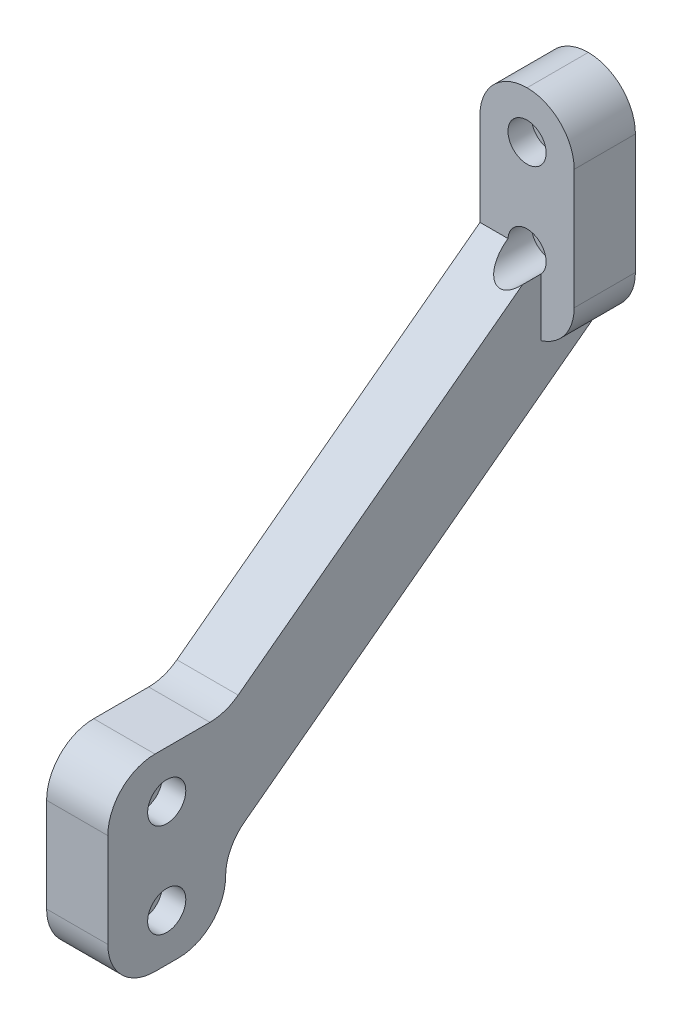
SolidWorks part; units mm, degrees
ref_plane "Alzado" through (0, 0, 0) normal (0, 0, 1) x (1, 0, 0)
ref_plane "Planta" through (0, 0, 0) normal (0, 1, 0) x (1, 0, 0)
ref_plane "Vista lateral" through (0, 0, 0) normal (1, 0, 0) x (0, 0, -1)
sketch "Croquis1" plane through (0, 0, 0) normal (1, 0, 0) x (0, 0, -1)
  line L0 (0, 0) -> (0, 40)
  line L1 (0, 40) -> (25, 40)
  line L2 (25, 40) -> (92, 90.25)
  line L3 (92, 90.25) -> (92, 120)
  line L4 (92, 120) -> (105, 120)
  line L5 (105, 120) -> (105, 75)
  line L7 (25, 0) -> (0, 0)
  line L8 (105, 75) -> (25, 15)
  line L9 (25, 15) -> (25, 0)
  dimension "D1" = 13
  dimension "D2" = 25
  dimension "D3" = 40
  dimension "D4" = 120
  dimension "D5" = 15
  dimension "D6" = 45
  dimension "D7" = 20
extrude "Saliente-Extruir1" add sketch "Croquis1" along normal blind 13
sketch "Croquis4" plane through (13, 0, 0) normal (1, 0, 0) x (0, 0, -1)
  line L0 (105, 75) -> (105, 120) construction
  line L1 (105, 120) -> (92, 120)
  line L2 (105, 120) -> (105, 75)
  line L3 (105, 75) -> (92, 75)
  line L4 (92, 120) -> (92, 75)
  line L5 (92, 120) -> (92, 90.25) construction
  point P5 (114.2102, 82.2348)
extrude "Saliente-Extruir2" add sketch "Croquis4" along normal blind 7
sketch "Croquis5" plane through (13, 0, 0) normal (1, 0, 0) x (0, 0, -1)
  line L0 (12.5, 40) -> (12.5, 0) construction
  line L1 (25, 40) -> (0, 40) construction
  line L2 (0, 0) -> (25, 0) construction
  circle A0 centre (12.5, 30) radius 2.125
  circle A1 centre (12.5, 10) radius 2.125
  dimension "D1" = 4.25
  dimension "D2" = 10
  dimension "D3" = 20
extrude "Cortar-Extruir1" cut sketch "Croquis5" against normal through all
sketch "Croquis6" plane through (13, 0, 0) normal (1, 0, 0) x (0, 0, -1)
  circle A0 centre (12.5, 30) radius 4.05
  circle A1 centre (12.5, 10) radius 4.05
  dimension "D1" = 8.1
extrude "Cortar-Extruir2" cut sketch "Croquis6" against normal blind 5
sketch "Croquis7" plane through (0, 0, -105) normal (0, 0, -1) x (-1, 0, 0)
  line L0 (-20, 120) -> (0, 120) construction
  line L1 (-10, 120) -> (-10, 75) construction
  line L2 (-13, 75) -> (0, 75) construction
  circle A0 centre (-10, 110) radius 2.125
  circle A1 centre (-10, 90) radius 2.125
  dimension "D1" = 4.25
  dimension "D2" = 10
  dimension "D3" = 20
extrude "Cortar-Extruir3" cut sketch "Croquis7" against normal up to next
sketch "Croquis8" plane through (0, 0, -105) normal (0, 0, -1) x (-1, 0, 0)
  circle A0 centre (-10, 110) radius 4.05
  circle A1 centre (-10, 90) radius 4.05
  dimension "D1" = 8.1
extrude "Cortar-Extruir4" cut sketch "Croquis8" against normal up to next from offset 8 offset against normal yes
fillet "Redondeo2" radius 10 1 edges at (6.5, 15, -25)
fillet "Redondeo5" radius 10 7 edges at (6.5, 0, 0) (6.5, 0, -25) (6.5, 40, -25) (6.5, 40, 0) (20, 75, -98.5) (0, 120, -98.5) (20, 120, -98.5)
